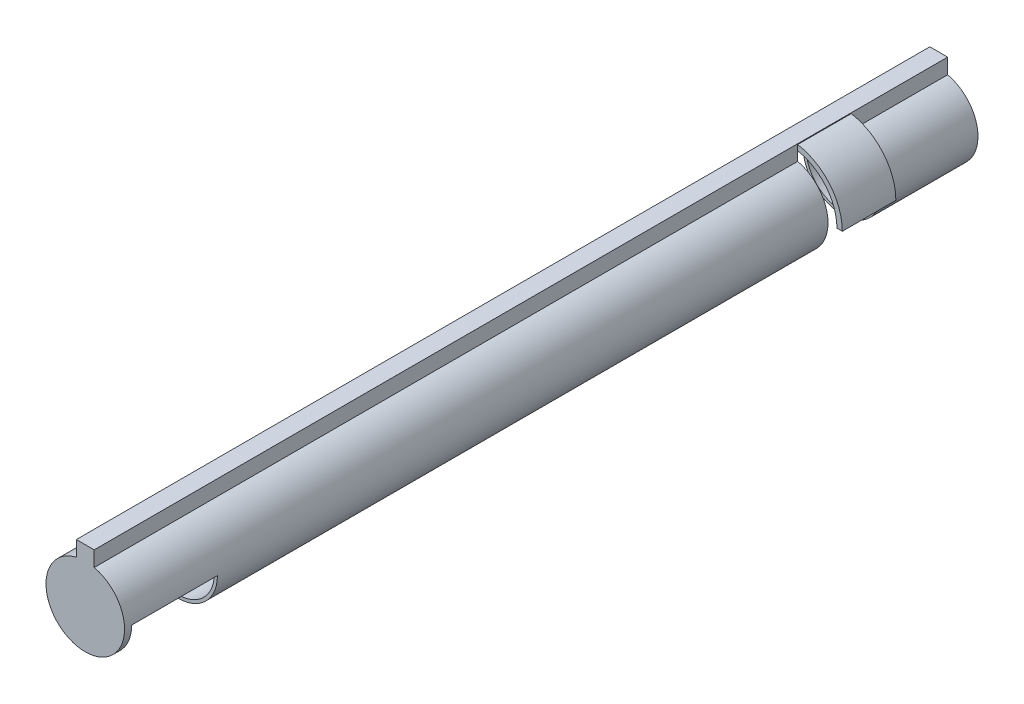
SolidWorks part; units mm, degrees
material "Manual Density from Real Component Plastica Fusoliera"
ref_plane "Piano frontale" through (0, 0, 0) normal (0, 0, 1) x (1, 0, 0)
ref_plane "Piano superiore" through (0, 0, 0) normal (0, 1, 0) x (1, 0, 0)
ref_plane "Piano destro" through (0, 0, 0) normal (1, 0, 0) x (0, 0, -1)
sketch "Schizzo1" plane through (0, 0, 0) normal (0, 0, 1) x (1, 0, 0)
  circle A0 centre (0, 0) radius 10.15
  circle A1 centre (0, 0) radius 11
  dimension "D1" = 20.3
  dimension "D2" = 22
extrude "Tubo" add sketch "Schizzo1" along normal blind 210
sketch "Schizzo2" plane through (0, 0, 210) normal (0, 0, 1) x (1, 0, 0)
  line L0 (0, -10.15) -> (0, -11)
  line L1 (10.15, 0) -> (11, 0)
  arc A0 (11, 0) -> (0, -11) centre (0, 0) ccw
  circle A1 centre (0, 0) radius 11 construction
  arc A2 (0, -10.15) -> (10.15, 0) centre (0, 0) cw
  circle A3 centre (0, 0) radius 10.15 construction
extrude "IngressoCavi" add sketch "Schizzo2" along normal blind 27
sketch "Schizzo4" plane through (0, 0, 210) normal (0, 0, 1) x (1, 0, 0)
  circle A0 centre (0, 0) radius 11
  circle A1 centre (0, 0) radius 6.5
  dimension "D1" = 22
  dimension "D2" = 13
extrude "FondoCorsa" add sketch "Schizzo4" along normal blind 3
sketch "Schizzo5" plane through (0, 0, 237) normal (0, 0, 1) x (1, 0, 0)
  circle A0 centre (0, 0) radius 11
  arc A1 (11, 0) -> (0, -11) centre (0, 0) ccw construction
extrude "Tappo" add sketch "Schizzo5" along normal blind 2
sketch "Schizzo6" plane through (0, 0, 0) normal (0, 0, 1) x (1, 0, 0)
  line L0 (-2.5, 11) -> (-2.5, 15)
  line L5 (2.5, 10.7121) -> (-2.5, 10.7121)
  line L6 (2.5, 10.7121) -> (2.5, 11)
  line L7 (2.5, 11) -> (-2.5, 11) construction
  line L8 (-2.5, 10.7121) -> (-2.5, 11)
  line L9 (-2.5, 15) -> (2.5, 15)
  line L10 (2.5, 15) -> (2.5, 11)
  circle A0 centre (0, 0) radius 11 construction
  point P4 (0, 11)
  dimension "D1" = 4
  dimension "D3" = 5
extrude "BaseInferiore" add sketch "Schizzo6" along normal up to surface (239 mm away) up to face at (11, 0, 239)
ref_plane "PianoInizioAnello" through (0, 0, 27) normal (0, 0, 1) x (1, 0, 0)
sketch "Schizzo7" plane through (0, 0, 27) normal (0, 0, 1) x (1, 0, 0)
  circle A0 centre (0, 0) radius 13.5
  dimension "D1" = 27
extrude "TaglioTubo" cut sketch "Schizzo7" along normal blind 15
sketch "Schizzo8" plane through (0, 0, 27) normal (0, 0, 1) x (1, 0, 0)
  line L0 (0, 13.5) -> (0, 0) construction
  line L1 (0, 0) -> (13.5, 0) construction
  line L2 (0, 13.5) -> (0, 15)
  line L3 (13.5, 0) -> (15, 0)
  line L4 (2.5, 15) -> (-2.5, 15) construction
  arc A0 (13.5, 0) -> (0, 13.5) centre (0, 0) ccw
  arc A1 (0, 15) -> (15, 0) centre (0, 0) cw
  dimension "D1" = 13.5
extrude "SupportoAnello" add sketch "Schizzo8" along normal blind 15
sketch "Schizzo9" plane through (0, 0, 210) normal (0, 0, -1) x (-1, 0, 0)
  line L0 (0, -10.15) -> (0, 0)
  line L1 (0, 0) -> (-10.15, 0)
  arc A0 (0, -10.15) -> (-10.15, 0) centre (0, 0) cw
  circle A1 centre (0, 0) radius 10.15 construction
extrude "FacilitazioneCavi" cut sketch "Schizzo9" against normal up to surface (3 mm away) up to face at (6.5, 0, 213)
fillet "RaccordoFacilitazioneCavi" radius 8 2 edges at (6.5, 0, 211.5) (0, -6.5, 211.5)
